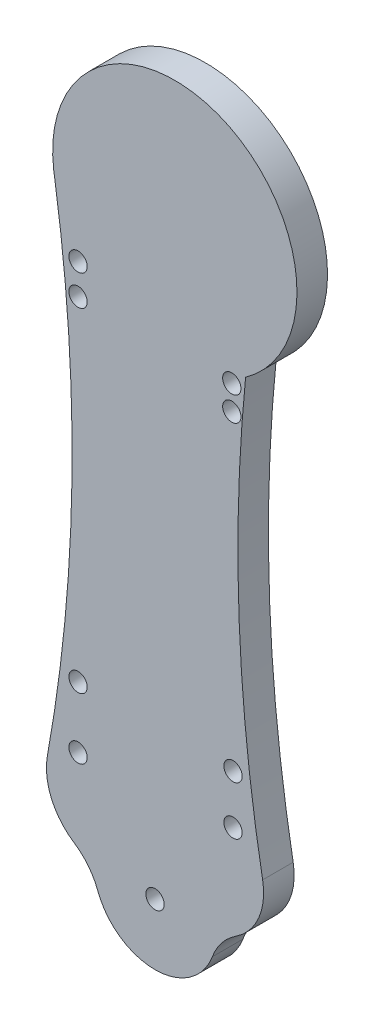
SolidWorks part; units mm, degrees
material "Acrílico (médio-alto impacto)"
ref_plane "Plano frontal" through (0, 0, 0) normal (0, 0, 1) x (1, 0, 0)
ref_plane "Plano superior" through (0, 0, 0) normal (0, 1, 0) x (1, 0, 0)
ref_plane "Plano direito" through (0, 0, 0) normal (1, 0, 0) x (0, 0, -1)
sketch "Esboço1" plane through (0, 0, 0) normal (0, 0, 1) x (1, 0, 0)
  line L0 (10, 0) -> (20, 0)
  line L1 (-20, 0) -> (-10, 0)
  line L2 (-16.3694, 93.6521) -> (-16.5765, 95.0244)
  arc A0 (-10, 0) -> (10, 0) centre (0, 0) ccw
  arc A1 (20, 0) -> (14.8299, 81.415) centre (263.5691, 56.3389) cw
  arc A2 (-20, 0) -> (-16.3694, 93.6521) centre (-263.5691, 56.3389) ccw
  arc A3 (14.8299, 81.415) -> (-16.4879, 94.4373) centre (3.2416, 97.7156) ccw
  dimension "D1" = 20
  dimension "D5" = 250
  dimension "D6" = 250
  dimension "D2" = 40
extrude "Ressalto-extrusão1" add sketch "Esboço1" along normal blind 5 contours A1 A3 L2 A2 L1 A0 L0 region at (0.9197, 55.6964, 0)
fillet "Filete3" radius 10 2 edges at (20, 0, 2.5) (-20, 0, 2.5)
fillet "Filete4" radius 10 2 edges at (-10, 0, 2.5) (10, 0, 2.5)
sketch "Esboço2" plane through (0, 0, 5) normal (0, 0, 1) x (1, 0, 0)
  circle A0 centre (0, 0) radius 1.5
extrude "Corte-extrusão1" cut sketch "Esboço2" against normal blind 5
sketch "Esboço3" plane through (0, 0, 5) normal (0, 0, 1) x (1, 0, 0)
  circle A0 centre (-12.6, 14.5) radius 1.5
  arc A1 (-9.3721, -3.4876) -> (9.3721, -3.4876) centre (0, 0) ccw construction
  circle A2 centre (-12.6, 24.5) radius 1.5
  circle A3 centre (-12.6, 79.11) radius 1.5
  circle A4 centre (-12.6, 84.11) radius 1.5
  circle A5 centre (0, 0) radius 1.5 construction
  point P5 (0, -10)
  dimension "D1" = 24.5
  dimension "D2" = 12.6
  dimension "D3" = 3
  dimension "D4" = 10
  dimension "D5" = 12.6
  dimension "D6" = 64.61
  dimension "D7" = 69.61
  dimension "D8" = 12.6
  dimension "D9" = 12.6
  dimension "D10" = 3
  dimension "D11" = 3
  dimension "D12" = 3
extrude "Corte-extrusão2" cut sketch "Esboço3" against normal through all
sketch "Esboço4" plane through (0, 0, 5) normal (0, 0, 1) x (1, 0, 0)
  circle A0 centre (12.57, 79.41) radius 1.5
  circle A1 centre (12.57, 75.41) radius 1.5
  circle A2 centre (12.77, 24.54) radius 1.5
  circle A3 centre (12.77, 16.54) radius 1.5
  circle A4 centre (0, 0) radius 1.5 construction
  dimension "D1" = 16.54
  dimension "D2" = 12.77
  dimension "D3" = 8
  dimension "D4" = 12.77
  dimension "D5" = 3
  dimension "D6" = 3
  dimension "D7" = 12.57
  dimension "D8" = 12.57
  dimension "D9" = 3
  dimension "D10" = 3
  dimension "D11" = 58.87
  dimension "D12" = 4
extrude "Corte-extrusão3" cut sketch "Esboço4" against normal blind 10
